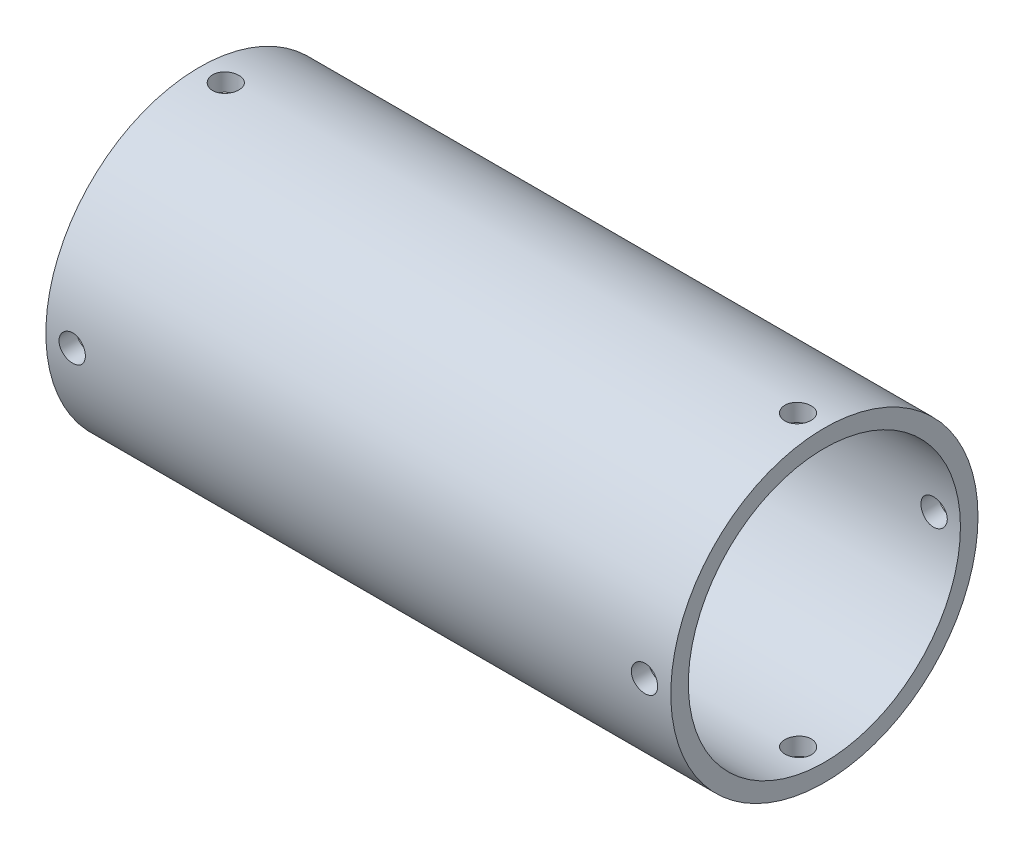
SolidWorks part; units mm, degrees
ref_plane "Спереди" through (0, 0, 0) normal (0, 0, 1) x (1, 0, 0)
ref_plane "Сверху" through (0, 0, 0) normal (0, 1, 0) x (1, 0, 0)
ref_plane "Справа" through (0, 0, 0) normal (1, 0, 0) x (0, 0, -1)
sketch "Эскиз1" plane through (0, 0, 0) normal (1, 0, 0) x (0, 0, -1)
  circle A0 centre (0, 0) radius 17.5
  circle A1 centre (0, 0) radius 15.5
  dimension "D1" = 35
  dimension "D2" = 31
extrude "Бобышка-Вытянуть1" add sketch "Эскиз1" along normal blind 71.2
sketch "Эскиз2" plane through (0, 0, 0) normal (0, 0, 1) x (1, 0, 0)
  line L0 (71.2, -17.5) -> (71.2, 17.5) construction
  line L1 (9.528, 0) -> (21.5106, 0)
  circle A0 centre (3, 0) radius 1.5
  circle A1 centre (68.2, 0) radius 1.5
  dimension "D1" = 3
  dimension "D2" = 3
  dimension "D3" = 3
  dimension "D4" = 3
extrude "Вырез-Вытянуть1" cut sketch "Эскиз2" against normal through all both and the other way through all contours A0 | A1 region at (3, 0, 0) region at (68.2, 0, 0)
pattern_circular "Круговой массив1" count 2 every 90 about axis through (9.528, 0, 0) along (1, 0, 0) of "Вырез-Вытянуть1"
